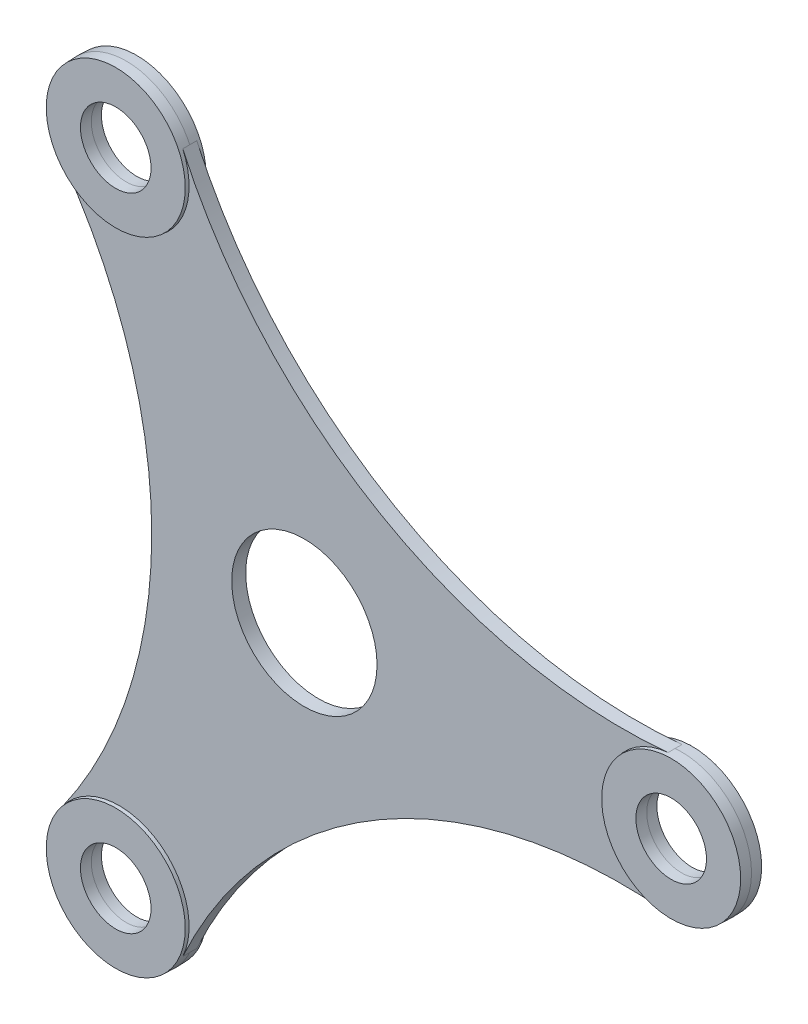
SolidWorks part; units mm, degrees
note: The reader was unsure of these and kept them because the rebuilt part matched: shared geometry of "Sketch1<3>".
ref_plane "Front Plane" through (0, 0, 0) normal (0, 0, 1) x (1, 0, 0)
ref_plane "Top Plane" through (0, 0, 0) normal (0, 1, 0) x (1, 0, 0)
ref_plane "Right Plane" through (0, 0, 0) normal (1, 0, 0) x (0, 0, -1)
sketch "Sketch1" plane through (0, 0, 0) normal (0, 0, 1) x (1, 0, 0)
  circle A0 centre (0, 0) radius 264.9731 construction
  circle A1 centre (0, 0) radius 52
  circle A2 centre (264.9731, 0) radius 25
  circle A3 centre (264.9731, 0) radius 50
  circle A4 centre (-132.4866, -229.4734) radius 50
  circle A5 centre (-132.4866, -229.4734) radius 25
  circle A6 centre (-132.4866, 229.4734) radius 50
  circle A7 centre (-132.4866, 229.4734) radius 25
  arc A8 (-87.0197, 250.2765) -> (260.2556, 49.777) centre (227.6108, 394.2335) ccw
  arc A9 (-87.0197, -250.2765) -> (260.2556, -49.777) centre (227.6108, -394.2335) cw
  arc A10 (-173.2359, 200.4995) -> (-173.2359, -200.4995) centre (-455.2216, 0) cw
  point P15 (0, 0)
  dimension "D1" = 3
  dimension "D2" = 104
  dimension "D3" = 100
  dimension "D4" = 50
  dimension "D5" = 346
  dimension "D6" = 346
  dimension "D7" = 346
  dimension "D8" = 396
extrude "Boss-Extrude1" add sketch "Sketch1" along normal mid plane 10 contours A6 A10 A4 A9 A3 A8 A1
extrude "Boss-Extrude2" add sketch "Sketch1<3>" along normal mid plane 15 draft 2 contours A6 A7 | A4 A5 | A3 A2
sketch "Sketch1<3>" plane through (0, 0, 0) normal (0, 0, 1) x (1, 0, 0) same geometry as "Sketch1"
